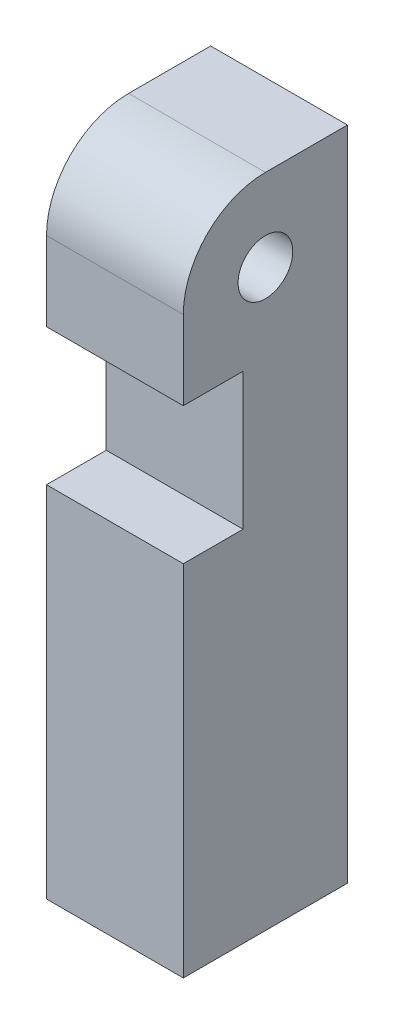
SolidWorks part; units mm, degrees
ref_plane "Front Plane" through (0, 0, 0) normal (0, 0, 1) x (1, 0, 0)
ref_plane "Top Plane" through (0, 0, 0) normal (0, 1, 0) x (1, 0, 0)
ref_plane "Right Plane" through (0, 0, 0) normal (1, 0, 0) x (0, 0, -1)
sketch "Elevator Paddle" plane through (0, 0, 0) normal (1, 0, 0) x (0, 0, -1)
  line L0 (3.81, 3.81) -> (3.81, -26.67)
  line L1 (3.81, -26.67) -> (-3.81, -26.67)
  line L2 (-3.81, -26.67) -> (-3.81, -10.016)
  line L3 (-6.4983, 38.1) -> (3.6147, 38.1)
  line L4 (3.81, 3.81) -> (0, 3.81)
  line L5 (-3.81, -3.666) -> (-1.0375, -3.666)
  line L6 (-1.0375, -3.666) -> (-1.0375, -10.016)
  line L7 (-1.0375, -10.016) -> (-3.81, -10.016)
  line L8 (-3.81, -3.666) -> (-3.81, 0)
  line L9 (1.735, 3.81) -> (1.735, -26.67) construction
  line L10 (-3.81, -12.8389) -> (1.735, -12.8389) construction
  line L11 (-1.0375, -10.016) -> (-1.0375, -12.8389) construction
  circle A0 centre (0, 0) radius 1.27
  arc A1 (0, 3.81) -> (-3.81, 0) centre (0, 0) ccw
  point P17 (-1.0375, -12.8389)
  dimension "D3" = 2.54
  dimension "D1" = 2.54
  dimension "D2" = 2.54
  dimension "D4" = 25.4
  dimension "D6" = 2.7725
  dimension "D7" = 2.54
  dimension "D5" = 6.35
  dimension "D8" = 2.075
extrude "Boss-Extrude1" add sketch "Elevator Paddle" along normal blind 6.35 contours L0 L1 L3 A0 region at (0, -12.3189, -0.2513)
equation "\"Ball Diameter\"= 1.75in"
equation "\"Sheet Thickness\"= 0.25in"
equation "\"Screw Diameter\"= .17in"
equation "\"Robot Diameter\"= 14in"
equation "\"Castor Screw Diameter\"= 0.22in"
equation "\"Wheel Diameter\" = 4in"
equation "\"Nut Diameter\" = 8.4mm"
equation "\"Nut Height\" = 2.9mm"
equation "\"Screw Height\" = 0.55in"
equation "\"D1@Boss-Extrude1\"=\"Sheet Thickness\""
equation "\"Pulley Diameter\" = 1in"
equation "\"Reactor Height\" = 14in"
equation "\"Elevator Height\" = 11.5in"
equation "\"Elevator Width\" = \"Ball Diameter\" + 0.25in"
equation "\"Elevator Bearing Diameter\" = sqr(2*(\"Sheet Thickness\"^2)) + 0.2in"
equation "\"Elevator Axle Endcap Diameter\" = \"Pulley Diameter\" + 0.25in"
equation "\"Elevator Axle Length\" = \"Elevator Width\" + 8*\"Sheet Thickness\""
equation "\"Elevator Clearance from Axis\" = 3.28in"
equation "\"D5@Elevator Paddle\"=\"Sheet Thickness\""
equation "\"D6@Elevator Paddle\"=\"Sheet Thickness\"/2"
equation "\"D8@Elevator Paddle\"=(\"Elevator Axle Endcap Diameter\"-\"Pulley Diameter\")/2 - 1.1mm"
